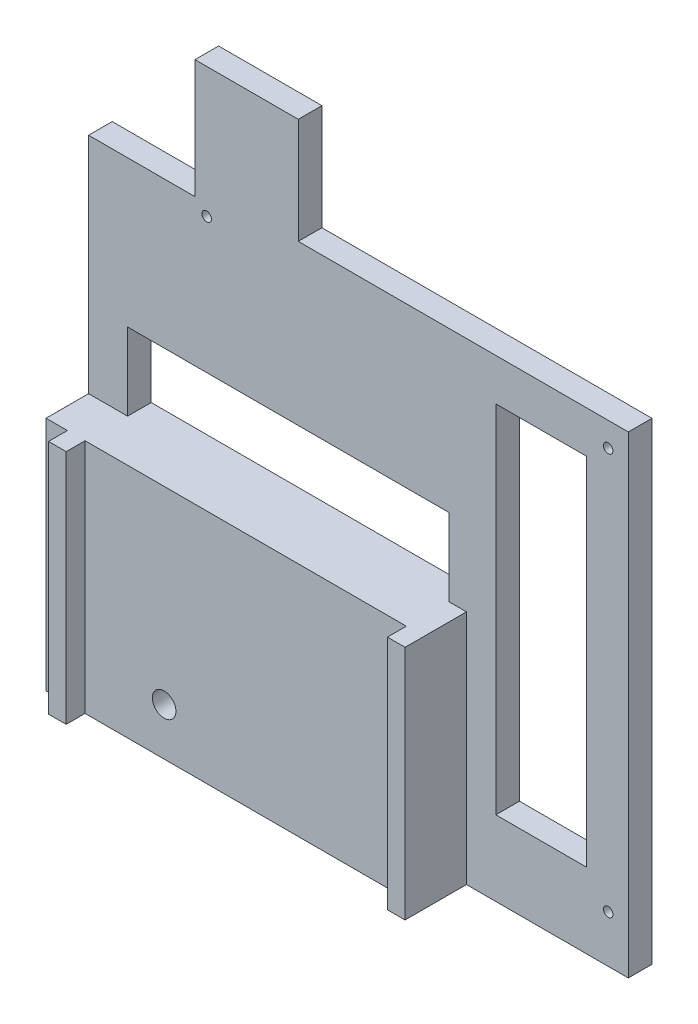
SolidWorks part; units mm, degrees
ref_plane "Plan de face" through (0, 0, 0) normal (0, 0, 1) x (1, 0, 0)
ref_plane "Plan de dessus" through (0, 0, 0) normal (0, 1, 0) x (1, 0, 0)
ref_plane "Plan de droite" through (0, 0, 0) normal (1, 0, 0) x (0, 0, -1)
sketch "Sketch1" plane through (0, 0, 0) normal (0, 0, 1) x (1, 0, 0)
  line L1 (-125, 122.5) -> (125, 122.5)
  line L2 (-125, 122.5) -> (-125, -122.5)
  line L3 (-125, -122.5) -> (125, -122.5)
  line L4 (125, 122.5) -> (125, -122.5)
  line L5 (-125, 122.5) -> (125, -122.5) construction
  line L6 (-125, -122.5) -> (125, 122.5) construction
  point P0 (0, 0)
  dimension "D1" = 245
  dimension "D2" = 250
extrude "Boss-Extrude1" add sketch "Sketch1" along normal blind 10
sketch "Sketch6" plane through (0, 0, 10) normal (0, 0, 1) x (1, 0, 0)
  line L5 (-125, -122.5) -> (35, -122.5)
  line L6 (-125, -122.5) -> (-125, -22.5)
  line L7 (-125, -22.5) -> (35, -22.5)
  line L8 (35, -122.5) -> (35, -22.5)
  dimension "D1" = 100
  dimension "D2" = 160
extrude "Boss-Extrude3" add sketch "Sketch6" along normal blind 18
sketch "Sketch7" plane through (0, 0, 28) normal (0, 0, 1) x (1, 0, 0)
  line L0 (35, -22.5) -> (-125, -22.5) construction
  line L1 (-115.96, -22.5) -> (-108.48, -22.5)
  line L2 (-115.96, -22.5) -> (-115.96, -122.5)
  line L3 (-115.96, -122.5) -> (-108.48, -122.5)
  line L4 (-108.48, -22.5) -> (-108.48, -122.5)
  line L5 (-125, -122.5) -> (35, -122.5) construction
  line L6 (35, -22.5) -> (-125, -22.5) construction
  line L7 (27.52, -22.5) -> (35, -22.5)
  line L8 (27.52, -22.5) -> (27.52, -122.5)
  line L9 (27.52, -122.5) -> (35, -122.5)
  line L10 (35, -22.5) -> (35, -122.5)
  point P14 (20.5, -22.5)
  dimension "D1" = 136
  dimension "D2" = 7.48
extrude "Boss-Extrude4" add sketch "Sketch7" along normal blind 8
sketch "Sketch8" plane through (0, 0, 0) normal (0, 0, -1) x (-1, 0, 0)
  line L0 (-27.52, -22.5) -> (-27.52, -122.5) construction
  line L1 (125, -122.5) -> (-27.52, -122.5)
  line L2 (125, -122.5) -> (125, -29.98)
  line L3 (125, -29.98) -> (-27.52, -29.98)
  line L4 (-27.52, -122.5) -> (-27.52, -29.98)
  line L6 (-35, -22.5) -> (125, -22.5) construction
  dimension "D1" = 7.48
extrude "Cut-Extrude2" cut sketch "Sketch8" against normal blind 20
sketch "Sketch9" plane through (0, 0, 20) normal (0, 0, -1) x (-1, 0, 0)
  line L0 (125, -122.5) -> (125, -29.98) construction
  line L1 (-27.52, -122.5) -> (125, -122.5) construction
  line L3 (64, -91.5) -> (86, -91.5)
  line L4 (64, -91.5) -> (64, -113.5)
  line L5 (64, -113.5) -> (86, -113.5)
  line L6 (86, -91.5) -> (86, -113.5)
  line L7 (64, -91.5) -> (86, -113.5) construction
  line L8 (64, -113.5) -> (86, -91.5) construction
  point P5 (75, -102.5)
  dimension "D1" = 22
  dimension "D2" = 22
  dimension "D3" = 50
  dimension "D4" = 20
extrude "Boss-Extrude5" add sketch "Sketch9" along normal blind 20
sketch "Sketch11" plane through (0, -113.5, 0) normal (0, -1, 0) x (1, 0, 0)
  line L0 (-64, 20) -> (-86, 20) construction
  line L1 (-84, 20) -> (-66, 20)
  line L2 (-84, 20) -> (-84, 10)
  line L3 (-84, 10) -> (-66, 10)
  line L4 (-66, 20) -> (-66, 10)
  line L5 (-86, 0) -> (-86, 20) construction
  line L6 (-64, 0) -> (-64, 20) construction
  line L7 (-64, 0) -> (-86, 0) construction
  dimension "D1" = 2
  dimension "D2" = 2
  dimension "D3" = 10
extrude "Cut-Extrude4" cut sketch "Sketch11" against normal blind 22
sketch "Sketch12" plane through (0, 0, 10) normal (0, 0, 1) x (1, 0, 0)
  line L1 (-125, 122.5) -> (-79.9506, 122.5)
  line L2 (-125, 122.5) -> (-125, 72.263)
  line L3 (-125, 72.263) -> (-79.9506, 72.263)
  line L4 (-79.9506, 122.5) -> (-79.9506, 72.263)
  line L5 (125, 122.5) -> (-36.2169, 122.5)
  line L7 (103.5258, 77.7297) -> (-36.2169, 77.7297)
  line L8 (-36.2169, 122.5) -> (-36.2169, 77.7297)
  line L13 (85.7686, 59.9629) -> (47.4328, 59.9629)
  line L15 (85.7686, -90.7132) -> (47.4328, -90.7132)
  line L23 (103.5258, 77.7297) -> (103.5258, -122.5)
  line L27 (85.7686, 59.9629) -> (85.7686, -90.7132)
  line L31 (47.4328, 59.9629) -> (47.4328, -90.7132)
  line L32 (35, -122.5) -> (125, -122.5) construction
  line L33 (103.5258, -122.5) -> (125, -122.5)
  line L34 (125, -122.5) -> (125, 122.5)
  line L35 (27.52, -22.5) -> (27.52, -122.5) construction
  line L36 (-108.48, -22.5) -> (27.52, -22.5)
  line L37 (-108.48, -22.5) -> (-108.48, 10.213)
  line L38 (-108.48, 10.213) -> (27.52, 10.213)
  line L39 (27.52, -22.5) -> (27.52, 10.213)
extrude "Cut-Extrude5" cut sketch "Sketch12" against normal through all
sketch "Sketch13" plane through (0, 0, 0) normal (0, 0, -1) x (-1, 0, 0)
  line L0 (64, -91.5) -> (86, -113.5) construction
  line L1 (86, -91.5) -> (64, -113.5) construction
  line L2 (75, -102.5) -> (75, 67.5) construction
  line L3 (75, 67.5) -> (-95, 67.5) construction
  line L4 (75, -102.5) -> (-95, -102.5) construction
  circle A0 centre (75, -102.5) radius 2
  circle A1 centre (-95, -102.5) radius 2
  circle A2 centre (75, 67.5) radius 2
  circle A3 centre (-95, 67.5) radius 2
  dimension "D1" = 170
  dimension "D4" = 4
  dimension "D5" = 4
  dimension "D6" = 4
  dimension "D2" = 170
  dimension "D3" = 170
extrude "Cut-Extrude6" cut sketch "Sketch13" against normal up to next
sketch "Sketch14" plane through (0, 0, 28) normal (0, 0, 1) x (1, 0, 0)
  circle A0 centre (-75, -102.5) radius 5
  dimension "D1" = 10
extrude "Cut-Extrude7" cut sketch "Sketch14" against normal up to next
